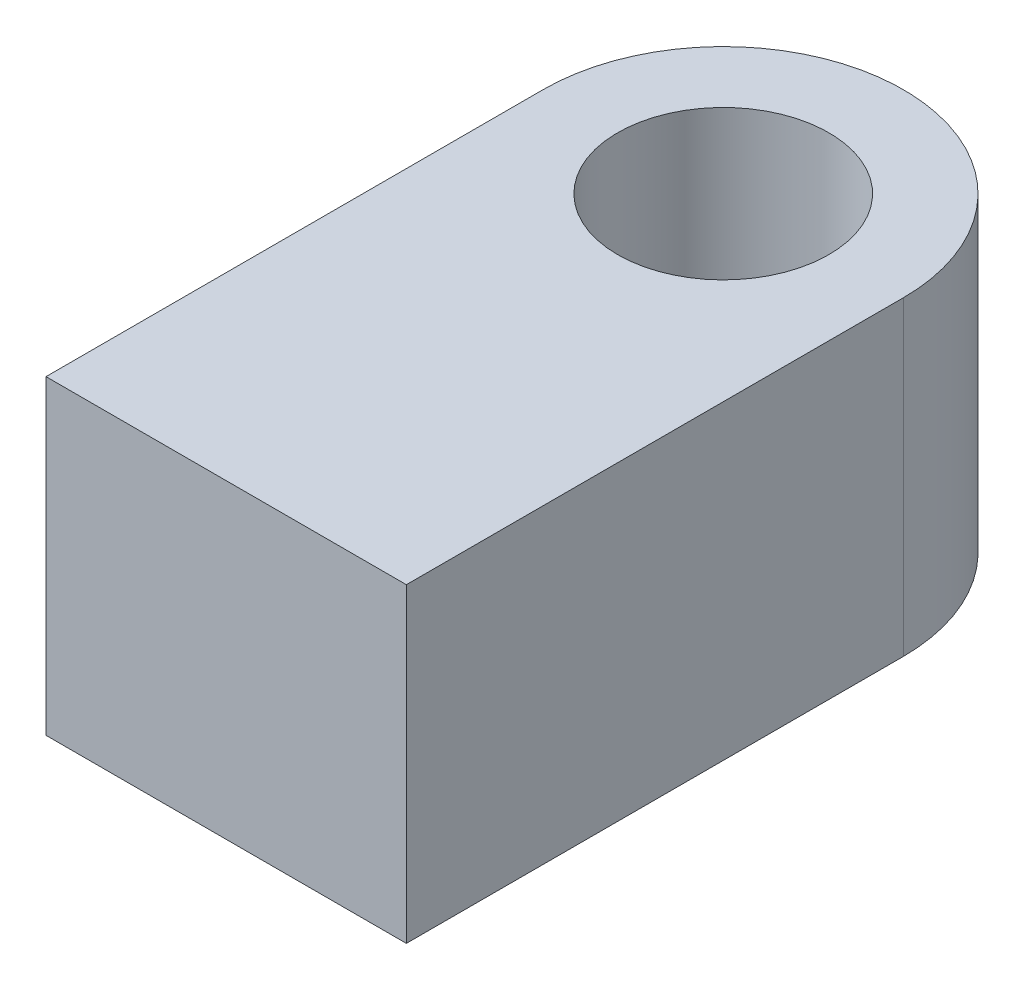
SolidWorks part; units mm, degrees
ref_plane "Front Plane" through (0, 0, 0) normal (0, 0, 1) x (1, 0, 0)
ref_plane "Top Plane" through (0, 0, 0) normal (0, 1, 0) x (1, 0, 0)
ref_plane "Right Plane" through (0, 0, 0) normal (1, 0, 0) x (0, 0, -1)
sketch "Sketch1" plane through (0, 0, 0) normal (0, 1, 0) x (1, 0, 0)
  line L0 (-14.5, 0) -> (-14.5, -40)
  line L1 (-14.5, -40) -> (14.5, -40)
  line L2 (14.5, -40) -> (14.5, 0)
  circle A0 centre (0, 0) radius 8.5
  arc A1 (14.5, 0) -> (-14.5, 0) centre (0, 0) ccw
  dimension "D1" = 29
  dimension "D2" = 17
  dimension "D3" = 40
extrude "Boss-Extrude1" add sketch "Sketch1" along normal blind 25
